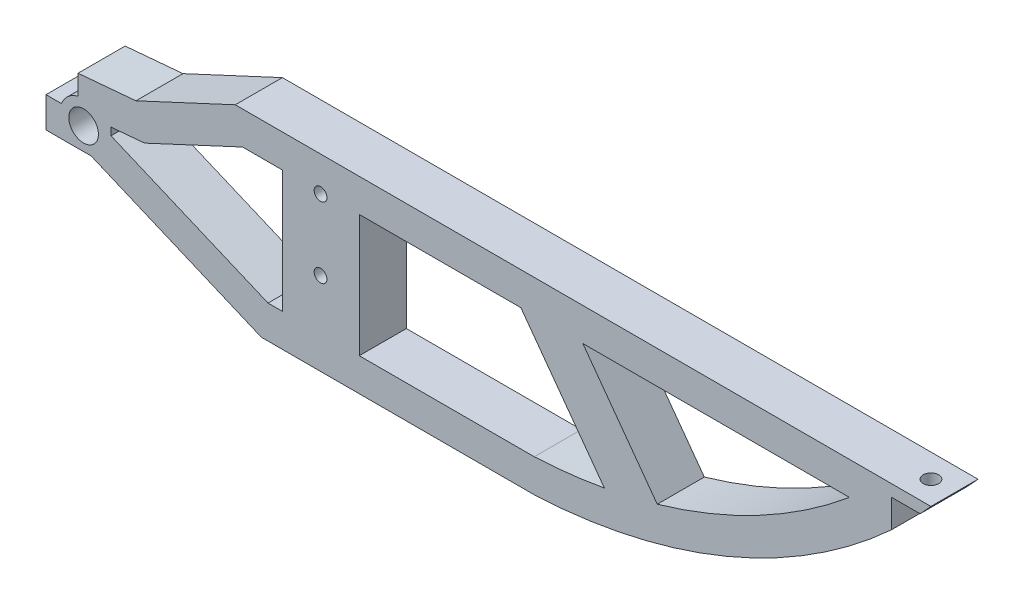
SolidWorks part; units mm, degrees
ref_plane "Front Plane" through (0, 0, 0) normal (0, 0, 1) x (1, 0, 0)
ref_plane "Top Plane" through (0, 0, 0) normal (0, 1, 0) x (1, 0, 0)
ref_plane "Right Plane" through (0, 0, 0) normal (1, 0, 0) x (0, 0, -1)
sketch "Sketch1" plane through (0, 0, 0) normal (0, 0, 1) x (1, 0, 0)
  line L1 (120.65, 25.4) -> (-120.65, 25.4)
  line L2 (120.65, 25.4) -> (120.65, -25.4)
  line L3 (120.65, -25.4) -> (-120.65, -25.4)
  line L4 (-120.65, 25.4) -> (-120.65, -25.4)
  line L5 (120.65, 25.4) -> (-120.65, -25.4) construction
  line L6 (120.65, -25.4) -> (-120.65, 25.4) construction
  point P0 (0, 0)
  dimension "D1" = 241.3
  dimension "D2" = 50.8
extrude "Boss-Extrude1" add sketch "Sketch1" along normal blind 12.7
sketch "Sketch3" plane through (0, 0, 12.7) normal (0, 0, 1) x (1, 0, 0)
  line L0 (0, 0) -> (-120.65, 0) construction
  line L1 (-120.65, 25.4) -> (-120.65, -25.4) construction
  circle A0 centre (-107.95, 0) radius 4
  dimension "D2" = 8
  dimension "D1" = 12.7
extrude "Cut-Extrude1" cut sketch "Sketch3" against normal through all
sketch "Sketch5" plane through (0, 0, 12.7) normal (0, 0, 1) x (1, 0, 0)
  line L0 (-120.65, -25.4) -> (120.65, -25.4) construction
  line L1 (-105.8942, -6.008) -> (-59.9903, -25.4)
  line L2 (-107.95, 6.35) -> (-67.0151, 25.4)
  line L3 (120.65, 25.4) -> (-120.65, 25.4) construction
  line L4 (-67.0151, 25.4) -> (-120.65, 25.4)
  line L5 (-120.65, 25.4) -> (-120.65, -25.4)
  line L6 (-120.65, -25.4) -> (-59.9903, -25.4)
  line L7 (120.65, 25.4) -> (120.65, -25.4)
  line L8 (120.65, -25.4) -> (0, -25.4)
  line L9 (-109.9582, -6.0241) -> (-105.8942, -6.008)
  line L10 (-118.0862, -6.0241) -> (-109.9582, -6.0241)
  line L11 (-118.0862, -6.0241) -> (-118.0862, 2.2309)
  line L12 (-118.0862, 2.2309) -> (-113.8952, 2.2309)
  arc A0 (0, -25.4) -> (120.65, 25.4) centre (6.9175, 126.8429) ccw
  arc A1 (-109.9582, -6.0241) -> (-105.8942, -6.008) centre (-107.95, 0) ccw construction
  arc A2 (-107.95, 6.35) -> (-113.8952, 2.2309) centre (-107.95, 0) ccw
  point P15 (-116.1445, -2.9908)
  line M3 (-120.65, 25.4) -> (-120.65, -25.4)
  line M4 (-120.65, -25.4) -> (120.65, -25.4)
  line M5 (120.65, -25.4) -> (120.65, 25.4)
  line M6 (120.65, 25.4) -> (-120.65, 25.4)
  dimension "D1" = 152.4
  dimension "D2" = 12.7
  dimension "D3" = 45.1505
  dimension "D4" = 45.9039
  dimension "D5" = 8.255
  dimension "D6" = 4.191
  dimension "D7" = 8.128
extrude "Cut-Extrude2" cut sketch "Sketch5" against normal through all contours A2 L2 L1 M6 M3 M4 | A0 L8 M5 region at (-83.2502, -16.4329, 12.7) region at (93.5193, -10.6939, 12.7)
sketch "Sketch6" plane through (0, 0, 12.7) normal (0, 0, 1) x (1, 0, 0)
  line L0 (-107.95, 0) -> (91.396, 0) construction
  arc A0 (13.8349, -25.4) -> (120.65, 25.4) centre (6.9175, 126.8429) ccw construction
  circle A1 centre (19.05, 0) radius 3.1347
  dimension "D1" = 127
sketch "Sketch7" plane through (0, 0, 0) normal (0, 0, -1) x (-1, 0, 0)
  line L0 (44.0204, -2.9977) -> (44.0204, 16.0523) construction
  point P3 (44.0204, -2.9977)
  point P4 (44.0204, 16.0523)
  dimension "D1" = 19.05
sketch "Sketch8" plane through (0, 0, 0) normal (0, 0, -1) x (-1, 0, 0)
  point P0 (44.0204, 16.0523)
  point P3 (44.0204, -2.9977)
hole_wizard "Tap Drill for #8-32 Tap1" positions "Sketch8" profile "Sketch9" hole size "#8-32" standard "ANSI Inch" end condition through all
sketch "Sketch9" plane through (-44.0204, 16.0523, 0) normal (1, 0, 0) x (0, 1, 0)
  line L0 (0, 0) -> (0, 12.7)
  line L1 (0, 12.7) -> (1.7272, 12.7)
  line L2 (1.7272, 12.7) -> (1.7272, 0)
  line L5 (1.7272, 0) -> (0, 0)
  line L11 (0, -6.35) -> (0, 107.95) construction
  dimension "Thru Hole Dia." = 3.4544
  dimension "Thru Hole Depth" = 12.7
ref_plane "Plane1" through (-114.3, 0, 0) normal (-1, 0, 0) x (0, 0, 1)
sketch "Sketch10" plane through (-114.3, 0, 0) normal (-1, 0, 0) x (0, 0, 1)
  line L0 (0, 0) -> (12.7, 0) construction
  line L1 (12.7, -3.1347) -> (12.7, 3.1347) construction
  circle A0 centre (6.0894, 0) radius 1.905
  dimension "D1" = 3.81
extrude "Cut-Extrude3" cut sketch "Sketch10" against normal blind 5.08
sketch "Sketch11" plane through (0, 0, 12.7) normal (0, 0, 1) x (1, 0, 0)
  line L0 (-93.8249, 12.9234) -> (-109.4459, 12.9234) construction
  line L1 (-107.95, 6.35) -> (-67.0151, 25.4) construction
  line L2 (-109.4459, 12.9234) -> (-109.4459, 5.6538) construction
  line L3 (-93.8249, 12.9234) -> (-109.4459, 5.6538)
  line L4 (-93.8249, 12.9234) -> (-109.4459, 11.5568)
  line L5 (-109.4459, 11.5568) -> (-109.4459, 5.6538)
  circle A1 centre (-107.95, 0) radius 4 construction
  dimension "D1" = 15.621
  dimension "D2" = 5.6538
  dimension "D3" = 175
extrude "Boss-Extrude2" add sketch "Sketch11" against normal up to surface (12.7 mm away) up to face at (-45.7476, 16.0523, 0)
sketch "Sketch12" plane through (0, 0, 12.7) normal (0, 0, 1) x (1, 0, 0)
  line L1 (10.0217, 16.51) -> (-33.5733, 16.51)
  line L24 (-33.5733, 16.51) -> (-33.5733, -16.51)
  line L25 (-54.2244, 16.51) -> (-54.2244, -16.51)
  line L26 (-54.2244, 16.51) -> (-65.0478, 16.51)
  line L27 (-33.5733, -16.51) -> (13.63, -16.51)
  line L28 (10.0217, 16.51) -> (32.5572, -14.3581)
  line L29 (26.7339, 16.51) -> (46.8231, -11.0072)
  line L30 (-100.5559, 3.4106) -> (-100.5559, 1.3876)
  line L31 (-100.5559, 1.3876) -> (-58.1896, -16.51)
  line L32 (-58.1896, -16.51) -> (13.63, -16.51)
  line L33 (98.6876, 16.51) -> (-65.0478, 16.51)
  line L34 (-65.0478, 16.51) -> (-91.492, 4.2036)
  line L35 (-91.492, 4.2036) -> (-100.5559, 3.4106)
  line L36 (-100.5559, 3.4106) -> (-100.5559, 1.3876)
  line L37 (-100.5559, 1.3876) -> (-58.1896, -16.51)
  line L38 (-58.1896, -16.51) -> (-54.2244, -16.51)
  line L39 (98.6876, 16.51) -> (26.7339, 16.51)
  line L40 (-65.0478, 16.51) -> (-91.492, 4.2036)
  line L41 (-91.492, 4.2036) -> (-100.5559, 3.4106)
  arc A0 (46.8231, -11.0072) -> (98.6876, 16.51) centre (6.9175, 126.8429) ccw
  arc A10 (13.63, -16.51) -> (98.6876, 16.51) centre (6.9175, 126.8429) ccw
  arc A11 (13.63, -16.51) -> (32.5572, -14.3581) centre (6.9175, 126.8429) ccw
  dimension "D1" = 8.89
extrude "Cut-Extrude4" cut sketch "Sketch12" against normal through all
sketch "Sketch13" plane through (0, 0, 12.7) normal (0, 0, 1) x (1, 0, 0)
  line L0 (-79.3724, -17.2121) -> (-87.4623, -19.4143)
  line L1 (-105.8942, -6.008) -> (-59.9903, -25.4) construction
  line L2 (-87.4623, -19.4143) -> (-89.1909, -13.0643)
  line L4 (-79.3724, -17.2121) -> (-89.1909, -13.0643)
  circle A0 centre (-107.95, 0) radius 4 construction
  dimension "D1" = 90
  dimension "D2" = 6.35
  dimension "D3" = 22.86
sketch "Sketch14" plane through (0.0221, -5.5891, 0) normal (0.004, -1, 0) x (1, 0.004, 0)
  line L0 (-109.9812, 0) -> (-109.9812, 12.7) construction
  line L2 (-109.9812, 6.35) -> (-105.9171, 6.35) construction
  line L3 (-105.9171, 0) -> (-105.9171, 12.7) construction
  line L4 (-107.9492, 0) -> (-107.9492, 12.7) construction
  line L5 (-109.9812, 0) -> (-105.9171, 0) construction
  line L6 (-109.9812, 12.7) -> (-105.9171, 12.7) construction
  circle A0 centre (-107.9492, 6.35) radius 1.27
  dimension "D1" = 2.54
extrude "Cut-Extrude5" cut sketch "Sketch14" against normal blind 6.35
sketch "Sketch15" plane through (0, 0, 12.7) normal (0, 0, 1) x (1, 0, 0)
  line L0 (117.6404, 22.225) -> (110.0327, 22.225)
  line L1 (120.65, 22.225) -> (57.15, 22.225) construction
  line L2 (110.0327, 22.225) -> (110.0327, 12.8153)
  line L3 (110.0327, 12.8153) -> (117.6404, 12.8153)
  line L4 (117.6404, 12.8153) -> (117.6404, 22.225)
extrude "Cut-Extrude6" cut sketch "Sketch15" against normal through all
sketch "Sketch16" plane through (0, 0, 12.7) normal (0, 0, 1) x (1, 0, 0)
  line L0 (117.7449, 22.225) -> (117.6404, 22.225)
  line L1 (120.65, 22.225) -> (57.15, 22.225) construction
  line L2 (117.6404, 22.225) -> (117.6404, 22.0792)
  line L3 (117.6404, 22.0792) -> (117.7449, 22.0792)
  line L4 (117.7449, 22.0792) -> (117.7449, 22.225)
  dimension "D1" = 0.1046
  dimension "D2" = 0.1458
extrude "Cut-Extrude8" cut sketch "Sketch16" against normal through all contours L4 L0 L2 L3
sketch "Sketch18" plane through (0, 25.4, 0) normal (0, 1, 0) x (1, 0, 0)
  circle A0 centre (114.3, -6.35) radius 2.0828
extrude "Cut-Extrude9" cut sketch "Sketch18" against normal through all contours A0
